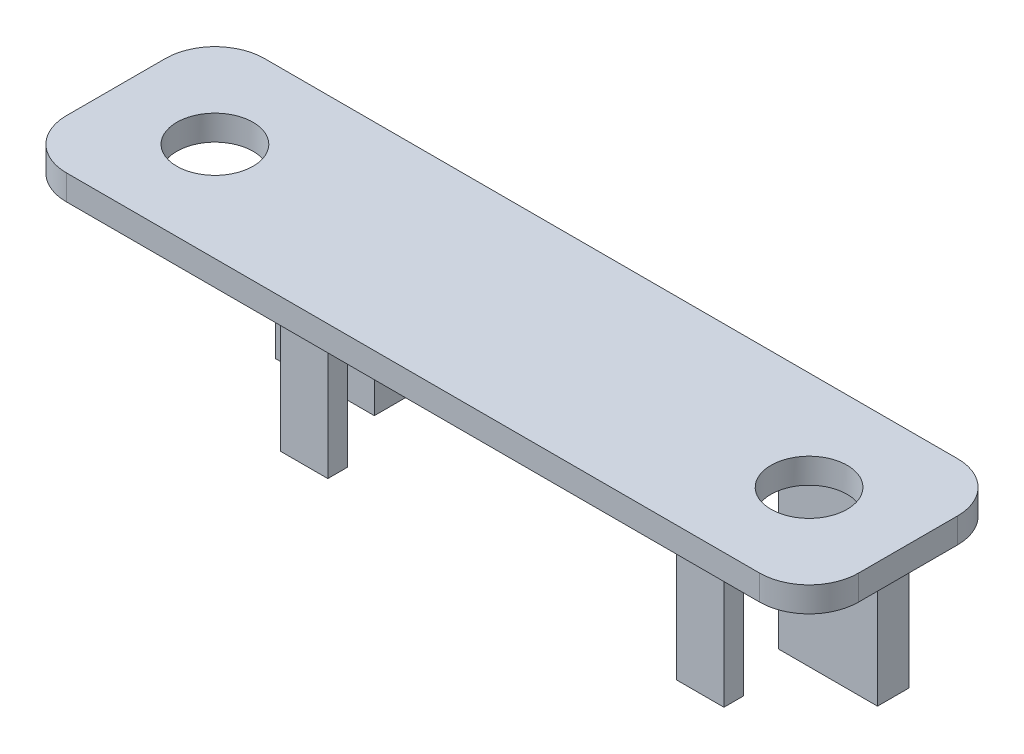
SolidWorks part; units mm, degrees
ref_plane "Front Plane" through (0, 0, 0) normal (0, 0, 1) x (1, 0, 0)
ref_plane "Top Plane" through (0, 0, 0) normal (0, 1, 0) x (1, 0, 0)
ref_plane "Right Plane" through (0, 0, 0) normal (1, 0, 0) x (0, 0, -1)
sketch "Sketch1" plane through (0, 0, 0) normal (0, 1, 0) x (1, 0, 0)
  line L1 (-40, -10) -> (40, -10)
  line L2 (-40, -10) -> (-40, 10)
  line L3 (-40, 10) -> (40, 10)
  line L4 (40, -10) -> (40, 10)
  line L5 (-40, -10) -> (40, 10) construction
  line L6 (-40, 10) -> (40, -10) construction
  point P0 (0, 0)
  dimension "D1" = 20
  dimension "D2" = 80
extrude "Boss-Extrude1" add sketch "Sketch1" along normal blind 2.54
sketch "Sketch2" plane through (0, 2.54, 0) normal (0, 1, 0) x (1, 0, 0)
  line L0 (-40, 0) -> (40, 0) construction
  line L1 (-40, 10) -> (-40, -10) construction
  line L2 (40, -10) -> (40, 10) construction
  line L3 (0, 0) -> (0, 10) construction
  line L4 (40, 10) -> (-40, 10) construction
  circle A0 centre (-30, 0) radius 3.85
  circle A1 centre (30, 0) radius 3.85
  dimension "D1" = 7.7
  dimension "D2" = 7.7
  dimension "D3" = 60
  dimension "D4" = 30
extrude "Cut-Extrude1" cut sketch "Sketch2" against normal blind 10
sketch "Sketch3" plane through (0, 0, -10) normal (0, 0, -1) x (-1, 0, 0)
  line L0 (-40, 2.54) -> (40, 2.54) construction
  line L1 (-23.5, 2.54) -> (-19.3221, 2.54)
  line L2 (-23.5, 2.54) -> (-23.5, 0)
  line L3 (-23.5, 0) -> (-19.3221, 0)
  line L4 (-19.3221, 2.54) -> (-19.3221, 0)
  line L5 (-40, 0) -> (40, 0) construction
  line L7 (13.1533, 2.54) -> (22, 2.54)
  line L8 (13.1533, 2.54) -> (13.1533, 0)
  line L9 (13.1533, 0) -> (22, 0)
  line L10 (22, 2.54) -> (22, 0)
  line L12 (-40, 2.54) -> (-40, 0) construction
  line L13 (40, 2.54) -> (40, 0) construction
  dimension "D1" = 16.5
  dimension "D2" = 18
extrude "Boss-Extrude2" [suppressed] add sketch "Sketch3" along normal blind 5
sketch "Sketch4" [suppressed] plane through (0, 0, 0) normal (0, -1, 0) x (1, 0, 0)
  line L0 (-13.1533, -15) -> (-13.1533, -10) construction
  line L1 (-22, -15) -> (-13.1533, -15)
  line L2 (-22, -15) -> (-22, -12.5)
  line L3 (-22, -12.5) -> (-13.1533, -12.5)
  line L4 (-13.1533, -15) -> (-13.1533, -12.5)
  line L5 (23.5, -15) -> (23.5, -10) construction
  line L6 (19.3221, -15) -> (23.5, -15)
  line L7 (19.3221, -15) -> (19.3221, -12.5)
  line L8 (19.3221, -12.5) -> (23.5, -12.5)
  line L9 (23.5, -15) -> (23.5, -12.5)
extrude "Boss-Extrude3" [suppressed] add sketch "Sketch4" along normal blind 15
sketch "Sketch5" plane through (0, 0, 0) normal (0, -1, 0) x (1, 0, 0)
  line L0 (-30, 0) -> (30, 0) construction
  line L10 (-22.4, -1) -> (-17.6, -1)
  line L11 (-22.4, -1) -> (-22.4, 1)
  line L12 (-22.4, 1) -> (-17.6, 1)
  line L13 (-17.6, -1) -> (-17.6, 1)
  line L14 (-22.4, -1) -> (-17.6, 1) construction
  line L15 (-22.4, 1) -> (-17.6, -1) construction
  line L16 (17.6, -1) -> (22.4, -1)
  line L17 (17.6, -1) -> (17.6, 1)
  line L18 (17.6, 1) -> (22.4, 1)
  line L19 (22.4, -1) -> (22.4, 1)
  line L20 (17.6, -1) -> (22.4, 1) construction
  line L21 (17.6, 1) -> (22.4, -1) construction
  point P0 (-20, 0)
  point P5 (20, 0)
  dimension "D1" = 4.8
  dimension "D2" = 2
  dimension "D3" = 10
  dimension "D4" = 10
  dimension "D5" = 4.8
  dimension "D6" = 2
extrude "Boss-Extrude4" add sketch "Sketch5" along normal blind 20
fillet "Fillet1" [suppressed] radius 10
sketch "Sketch7" plane through (0, 0, 0) normal (0, -1, 0) x (1, 0, 0)
  line L0 (-40, -10) -> (-40, 10) construction
  line L1 (-30.75, -10.0161) -> (30.06, -10.0161)
  line L2 (-30.75, -10.0161) -> (-30.75, -6.85)
  line L3 (-30.75, -6.85) -> (30.06, -6.85)
  line L4 (30.06, -10.0161) -> (30.06, -6.85)
  line L5 (40, 10) -> (40, -10) construction
  circle A0 centre (-30, 0) radius 3.85 construction
  dimension "D1" = 6.85
  dimension "D2" = 9.25
  dimension "D3" = 9.94
extrude "Boss-Extrude5" add sketch "Sketch7" along normal blind 20
sketch "Sketch8" plane through (0, 0, -10.0161) normal (0, 0, -1) x (-1, 0, 0)
  line L0 (30.75, -20) -> (-30.06, -20) construction
  line L1 (-20.06, -20) -> (20.75, -20)
  line L2 (-20.06, -20) -> (-20.06, 0)
  line L3 (-20.06, 0) -> (20.75, 0)
  line L4 (20.75, -20) -> (20.75, 0)
  line L5 (-30.06, -20) -> (-30.06, 0) construction
  line L6 (30.75, -20) -> (30.75, 0) construction
  line L7 (-30.06, 0) -> (30.75, 0) construction
  dimension "D1" = 10
  dimension "D2" = 10
  dimension "D3" = 0
extrude "Cut-Extrude2" cut sketch "Sketch8" against normal up to surface (3.1661 mm away) up to face at (-0.345, -10, -6.85)
fillet "Fillet2" radius 5 4 edges at (-40, 1.27, -10) (-40, 1.27, 10) (40, 1.27, 10) (40, 1.27, -10)
